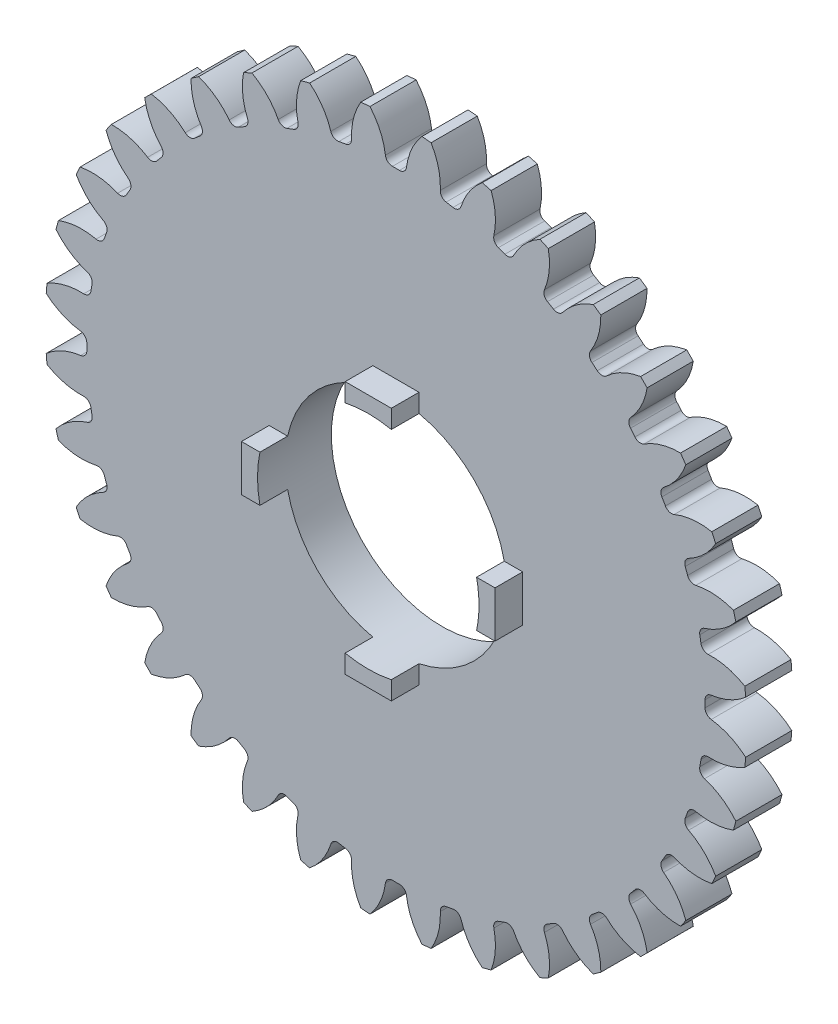
SolidWorks part; units mm, degrees
ref_plane "Front Plane" through (0, 0, 0) normal (0, 0, 1) x (1, 0, 0)
ref_plane "Top Plane" through (0, 0, 0) normal (0, 1, 0) x (1, 0, 0)
ref_plane "Right Plane" through (0, 0, 0) normal (1, 0, 0) x (0, 0, -1)
sketch "Sketch1" plane through (0, 0, 0) normal (0, 0, 1) x (1, 0, 0)
  line L4 (-1.0859, 33.4824) -> (0, 0) construction
  line L5 (0, 0) -> (0, 38) construction
  line L6 (0, 0) -> (3.3119, 37.8554) construction
  line L7 (-1.6208, 35.9635) -> (0.7881, 36.9653) construction
  line L8 (-1.6208, 35.9635) -> (0.4023, 36.0547) construction
  line L11 (1.6208, 35.9635) -> (-1.6208, 35.9635) construction
  circle A0 centre (0, 0) radius 33.5
  circle A1 centre (0, 0) radius 36 construction
  circle A2 centre (0, 0) radius 38
  arc A3 (-2.8135, 37.8957) -> (-1.0859, 33.4824) centre (-8.1739, 33.2525) cw
  arc A4 (2.8135, 37.8957) -> (1.0859, 33.4824) centre (8.1739, 33.2525) ccw
  point P5 (-36, 0)
  point P6 (-38, 0)
  point P7 (-33.5, 0)
  point P12 (-1.6208, 35.9635)
  point P22 (1.6208, 35.9635)
  dimension "D5" = 72
  dimension "D1" = 2.5
  dimension "D2" = 2
  dimension "D3" = 20
  dimension "D4" = 3.2416
  dimension "D6" = 5
  dimension "D7" = 0.5
extrude "Boss-Extrude1" add sketch "Sketch1" against normal blind 5 contours A2
extrude "Cut-Extrude1" cut sketch "Sketch1<4>" against normal blind 10 contours A4 A2 A3 A0 region at (0, 36.1155, 0)
sketch "Sketch1<4>" plane through (0, 0, 0) normal (0, 0, 1) x (1, 0, 0) same geometry as "Sketch1"
fillet "Fillet2" radius 0.76 2 edges at (1.0859, 33.4824, -2.5) (-1.0859, 33.4824, -2.5)
ref_axis "Axis1" through (0, 0, 0) along (0, 0, 1)
pattern_circular "CirPattern2" count 36 over 360 about axis through (0, 0, 0) along (0, 0, 1) of "Cut-Extrude1", "Fillet2"
sketch "Sketch2" plane through (0, 0, 0) normal (0, 0, 1) x (1, 0, 0)
  circle A0 centre (0, 0) radius 12
  dimension "D1" = 24
extrude "Cut-Extrude2" cut sketch "Sketch2" against normal up to surface (5 mm away) up to face at (0, 0, -5)
sketch "Sketch3" plane through (0, 0, 0) normal (0, 0, 1) x (1, 0, 0)
  line L0 (-2.5, 11.7367) -> (-2.5, 13.7367)
  line L1 (-2.5, 13.7367) -> (2.5, 13.7367)
  line L2 (2.5, 13.7367) -> (2.5, 11.7367)
  line L3 (0, 0) -> (0, 12) construction
  line L4 (13.7367, -2.5) -> (11.7367, -2.5)
  line L5 (13.7367, 2.5) -> (13.7367, -2.5)
  line L6 (11.7367, 2.5) -> (13.7367, 2.5)
  line L7 (-2.5, -13.7367) -> (-2.5, -11.7367)
  line L8 (2.5, -13.7367) -> (-2.5, -13.7367)
  line L9 (2.5, -11.7367) -> (2.5, -13.7367)
  line L10 (-13.7367, 2.5) -> (-11.7367, 2.5)
  line L11 (-13.7367, -2.5) -> (-13.7367, 2.5)
  line L12 (-11.7367, -2.5) -> (-13.7367, -2.5)
  circle A0 centre (0, 0) radius 12 construction
  arc A1 (-2.5, 11.7367) -> (2.5, 11.7367) centre (0, 0) cw
  arc A2 (11.7367, 2.5) -> (11.7367, -2.5) centre (0, 0) cw
  arc A3 (2.5, -11.7367) -> (-2.5, -11.7367) centre (0, 0) cw
  arc A4 (-11.7367, -2.5) -> (-11.7367, 2.5) centre (0, 0) cw
  point P24 (0, 0)
  dimension "D4" = 4
  dimension "D1" = 2.5
  dimension "D2" = 2.5
  dimension "D3" = 2
extrude "Boss-Extrude2" add sketch "Sketch3" along normal blind 3
equation "\"backlash\"= 0.1mm"
equation "\"module\"= 2mm"
equation "\"pressureAngle\"= 20deg"
equation "\"width\"= 10mm"
equation "\"D1@Sketch1\"= 1.25 * \"module\""
equation "\"D2@Sketch1\"=\"module\""
equation "\"D5@Sketch1\"=\"module\"*\"numberOfTeeth\""
equation "\"D1@Boss-Extrude1\"=\"width\"-5"
equation "\"D3@Sketch1\"=\"pressureAngle\""
equation "\"D1@Cut-Extrude1\"=\"width\""
equation "\"D1@CirPattern2\"=\"numberOfTeeth\""
equation "\"D1@Fillet2\"=0.38*\"module\""
equation "\"D4@Sketch1\"=pi*\"module\"/2+\"backlash\""
equation "\"numberOfTeeth\"= 36"
equation "\"D6@Sketch1\"=180/\"numberOfTeeth\""
equation "\"toothTipProfile\"= 1mm"
equation "\"D7@Sketch1\"=\"toothTipProfile\"/2"
equation "\"lengthOverallRack\"= pi * \"module\" * \"numberOfTeethRack\""
equation "\"numberOfTeethRack\"= 20"
